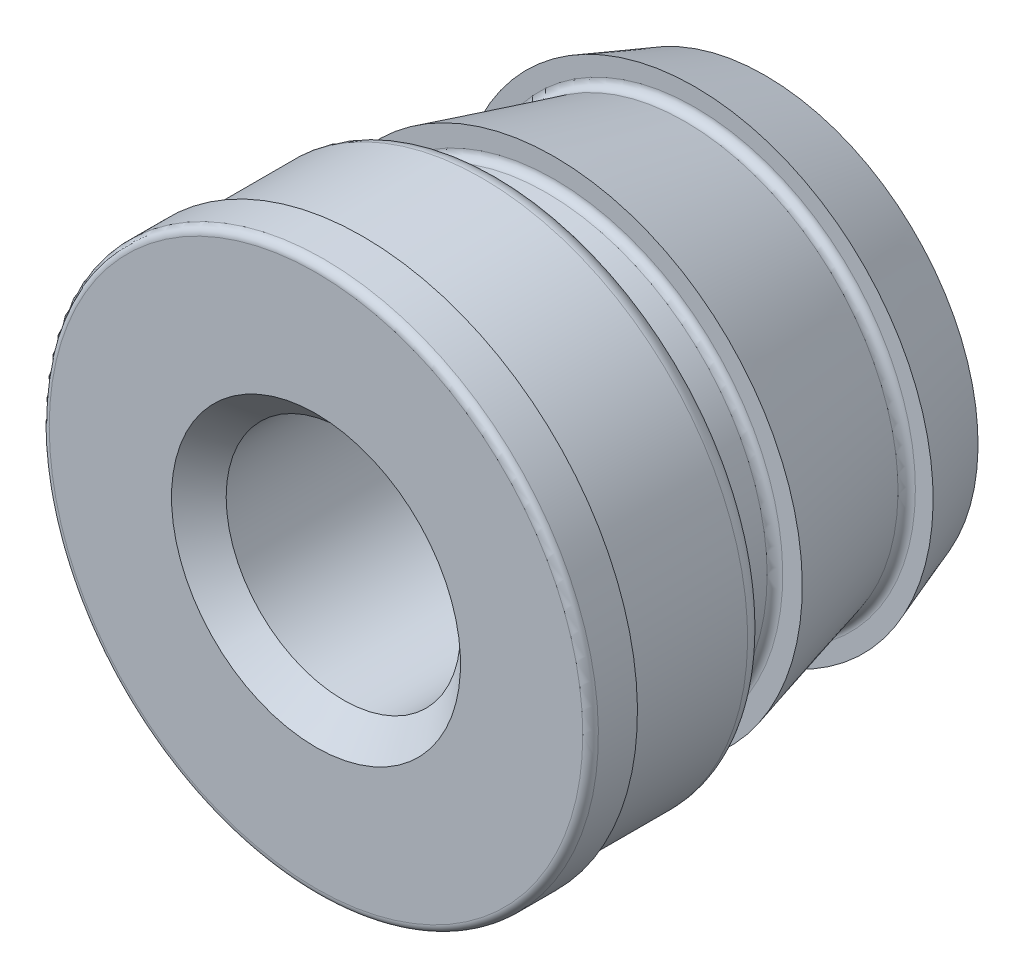
SolidWorks part; units mm, degrees
material "Brass"
ref_plane "Front Plane" through (0, 0, 0) normal (0, 0, 1) x (1, 0, 0)
ref_plane "Top Plane" through (0, 0, 0) normal (0, 1, 0) x (1, 0, 0)
ref_plane "Right Plane" through (0, 0, 0) normal (1, 0, 0) x (0, 0, -1)
sketch "Sketch1" plane through (0, 0, 0) normal (1, 0, 0) x (0, 0, -1)
  line L0 (1.4605, 0) -> (-1.4605, 0) construction
  line L1 (-1.4605, 1.7856) -> (-1.4605, -1.7856) construction
  line L2 (1.0033, -1.5494) -> (1.0033, 1.5494) construction
  line L3 (1.4605, 1.3843) -> (1.4605, -1.3843) construction
  line L4 (-1.4605, 1.7856) -> (-1.1557, 1.7856) construction
  line L5 (-1.1557, 1.7856) -> (-1.1557, 1.7272) construction
  line L6 (-1.1557, 1.7272) -> (-0.2667, 1.7272) construction
  line L7 (-0.2667, 1.7272) -> (-0.2667, 1.4351) construction
  line L8 (-0.2667, 1.4351) -> (0.0889, 1.4351) construction
  line L9 (0.0889, 1.4351) -> (0.0889, 1.6129) construction
  line L10 (0.0889, 1.6129) -> (1.0033, 1.3679) construction
  line L12 (-1.4605, -0.9398) -> (-1.2827, -0.762) construction
  line L13 (-1.2827, -0.762) -> (1.2827, -0.762) construction
  line L14 (1.2827, -0.762) -> (1.4605, -0.9398) construction
  line L15 (-1.2827, -0.762) -> (-1.2827, -0.4445) construction
  point P4 (0, 0)
  point P11 (1.0033, 0)
  dimension "Diameter (A)" = 3.5712
  dimension "Diameter (B)" = 3.0988
  dimension "End OD" = 2.7686
  dimension "Installed Length" = 2.921
  dimension "Head Length" = 0.3048
  dimension "Knurl Band OD" = 3.4544
  dimension "Knurl Band Length" = 0.889
  dimension "Relief Depth" = 0.2921
  dimension "Relief Length" = 0.3556
  dimension "Barb Length" = 0.9144
  dimension "Barb OD" = 3.2258
  dimension "Barb Angle" = 15
  dimension "Thread Size" = 1.524
  dimension "Thread Pitch" = 0.3175
  dimension "C'Sink" = 45
  dimension "C'Sink Dia" = 1.8796
sketch "Sketch2" plane through (0, 0, 0) normal (1, 0, 0) x (0, 0, -1)
  line L0 (1.4605, 0) -> (-1.4605, 0) construction
  line L1 (1.4605, 0) -> (-1.4605, 0) construction
  line L2 (-1.4605, 0.9398) -> (-1.4605, 1.7348)
  line L3 (-1.4605, 1.7856) -> (-1.4605, -1.7856) construction
  line L4 (-1.4097, 1.7856) -> (-1.1557, 1.7856)
  line L5 (-1.1557, 1.7856) -> (-1.1557, 1.7272)
  line L6 (-1.1557, 1.7272) -> (-0.381, 1.7272)
  line L7 (-0.2667, 1.6129) -> (-0.2667, 1.4859)
  line L8 (-0.2159, 1.4351) -> (0.0381, 1.4351)
  line L9 (0.0889, 1.4859) -> (0.0889, 1.6129)
  line L10 (0.0889, 1.6129) -> (0.9394, 1.385)
  line L11 (1.0033, 1.4341) -> (1.0033, 1.5494)
  line L15 (0.0889, 1.6129) -> (-0.2667, 1.6129) construction
  line L17 (1.0033, 1.5494) -> (1.4605, 1.3843)
  line L18 (1.4605, 1.3843) -> (1.4605, 0.9398)
  line L19 (1.4605, 1.3843) -> (1.4605, -1.3843) construction
  line L20 (1.4605, 0.9398) -> (1.2827, 0.762)
  line L21 (1.2827, 0.762) -> (-1.2827, 0.762)
  line L31 (1.2827, -0.762) -> (1.2827, 0.762) construction
  line L32 (-1.4605, 0.9398) -> (-1.2827, 0.762)
  line L33 (-1.4605, -0.9398) -> (-1.2827, -0.762) construction
  line L34 (1.2827, -0.762) -> (1.4605, -0.9398) construction
  arc A0 (-0.381, 1.7272) -> (-0.2667, 1.6129) centre (-0.381, 1.6129) cw
  arc A1 (-1.4605, 1.7348) -> (-1.4097, 1.7856) centre (-1.4097, 1.7348) cw
  arc A2 (0.9394, 1.385) -> (1.0033, 1.4341) centre (0.9525, 1.4341) ccw
  arc A3 (0.0381, 1.4351) -> (0.0889, 1.4859) centre (0.0381, 1.4859) ccw
  arc A4 (-0.2667, 1.4859) -> (-0.2159, 1.4351) centre (-0.2159, 1.4859) ccw
  point P23 (-0.2667, 1.7272)
  point P26 (-1.4605, 1.7856)
  point P37 (1.0033, 1.3679)
  point P42 (0.0889, 1.4351)
  point P45 (1.2827, 0)
  point P52 (-0.2667, 1.4351)
  dimension "D1" = 0.0508
  dimension "D2" = 0.0508
revolve "Revolve1" add sketch "Sketch2" angle 360 about L1
sketch "Sketch3" plane through (0, 0, 1.4605) normal (0, 0, 1) x (1, 0, 0)
  line L0 (0, -0.762) -> (0, 0) construction
  line L1 (0, 0) -> (0.381, -0.6599) construction
  circle A0 centre (0, 0) radius 0.762 construction
  point P0 (0.381, -0.6599)
  dimension "D1" = 30
sketch "Sketch4" [suppressed] plane through (0, 0, 1.4605) normal (0, 0, 1) x (1, 0, 0)
  circle A0 centre (0, 0) radius 0.762 construction
  circle A1 centre (0, 0) radius 0.762
curve "Helix/Spiral1" [suppressed] pitch 0.3175 height 3.2385 turns 10.2
sketch "Sketch5" [suppressed] plane through (0, 0, 0) normal (1, 0, 0) x (0, 0, -1)
  line L0 (-1.7582, 0.7792) -> (-1.5994, 0.5042) construction
  line L1 (-1.5994, 0.5042) -> (-1.4407, 0.7792) construction
  line L2 (-1.4407, 0.7792) -> (-1.7582, 0.7792) construction
  line L3 (-1.7383, 0.7448) -> (-1.4605, 0.7448) construction
  line L4 (-1.5994, 0.7792) -> (-1.5994, 0.7448) construction
  line L5 (-1.5994, 0.7448) -> (-1.5994, 0.5386) construction
  line L6 (-1.5994, 0.5386) -> (-1.5994, 0.5042) construction
  line L7 (-1.6192, 0.5386) -> (-1.5796, 0.5386)
  line L8 (-1.7482, 0.762) -> (-1.4506, 0.762)
  line L9 (-1.5796, 0.5386) -> (-1.4506, 0.762)
  line L10 (-1.6192, 0.5386) -> (-1.7482, 0.762)
  line L11 (-1.4605, 1.7856) -> (-1.4605, -1.7856) construction
  line L12 (1.2827, 0.762) -> (-1.2827, 0.762) construction
  point P12 (-1.5994, 0.762)
  dimension "D1" = 0.3175
  dimension "D2" = 0.0397
sweep "Sweep1" [suppressed] add profiles "Sketch5" path "Helix/Spiral1"
sketch "Sketch6" [suppressed] plane through (0, 0, 1.4605) normal (0, 0, 1) x (1, 0, 0)
  circle A0 centre (0, 0) radius 0.9398
extrude "Cut-Extrude1" [suppressed] cut sketch "Sketch6" against normal through all draft 45 and the other way through all
sketch "Sketch7" [suppressed] plane through (0, 0, -1.4605) normal (0, 0, -1) x (-1, 0, 0)
  circle A0 centre (0, 0) radius 0.9398 construction
  circle A1 centre (0, 0) radius 0.9398
extrude "Cut-Extrude2" [suppressed] cut sketch "Sketch7" against normal through all draft 45 and the other way through all
ref_plane "Plane2" [suppressed] through (0, 0, 1.1557) normal (0, 0, 1) x (1, 0, 0)
sketch "Sketch8" [suppressed] plane through (0, 0, 1.1557) normal (0, 0, 1) x (1, 0, 0)
  line L1 (-0.0359, 1.7123) -> (-0.1416, 1.6067)
  line L4 (0.1416, 1.6067) -> (0.0359, 1.7123)
  line L5 (-0.0533, 1.4242) -> (0.0029, 1.4805) [skipped]
  line L6 (-0.2728, 1.7504) -> (-0.2691, 1.7467) [skipped]
  circle A0 centre (0, 1.6129) radius 0.0957 construction
  circle A2 centre (0, 0) radius 1.6129 construction
  circle A3 centre (0, 0) radius 1.6129 construction
  arc A5 (0.1416, 1.6067) -> (-0.1416, 1.6067) centre (0, 0) ccw
  arc A6 (-0.0359, 1.7123) -> (0.0359, 1.7123) centre (0, 1.6764) cw
  circle A7 centre (0, 0) radius 1.7272 construction
  dimension "D1" = 0.0508
sketch "Sketch9" [suppressed] plane through (0, 0, 1.1557) normal (0, 0, 1) x (1, 0, 0)
  circle A0 centre (0, 0) radius 1.7272 construction
  circle A1 centre (0, 0) radius 1.7272
curve "Helix/Spiral2" [suppressed] pitch 19.3964 height 1.0668 turns 0.055
sketch "Sketch10" [suppressed] plane through (0, 0, 1.1557) normal (0, 0, -1) x (-1, 0, 0)
  circle A0 centre (0, 0) radius 1.6129 construction
  circle A1 centre (0, 0) radius 1.6129
  circle A2 centre (0, 0) radius 1.7272 construction
  circle A3 centre (0, 0) radius 1.7272
extrude "Cut-Extrude3" [suppressed] cut sketch "Sketch10" along normal up to surface (0.889 mm away)
sweep "Sweep2" [suppressed] add profiles "Sketch8" path "Helix/Spiral2"
pattern_circular "CirPattern1" [suppressed] count 16 over 360 of bodies 115
mirror "Mirror1" [suppressed] about plane through (0, 0, 0) normal (1, 0, 0)
sketch "Sketch11" [suppressed] plane through (0, 0, 0) normal (1, 0, 0) x (0, 0, -1)
  line L1 (-0.2667, 1.6129) -> (-0.2667, 1.4859)
  line L4 (-0.381, 1.7272) -> (-0.381, 1.7856)
  line L5 (-0.381, 1.7856) -> (0.0889, 1.7856)
  line L6 (0.0889, 1.7856) -> (0.0889, 1.4859)
  line L7 (-1.4097, 1.7856) -> (-1.1557, 1.7856) construction
  line L8 (1.4605, 0) -> (-1.4605, 0) construction
  line L9 (1.4605, 0) -> (-1.4605, 0) construction
  line L10 (-0.2159, 1.4351) -> (0.0381, 1.4351) construction
  line L11 (-0.2159, 1.4351) -> (0.0381, 1.4351)
  arc A0 (-0.2667, 1.6129) -> (-0.381, 1.7272) centre (-0.381, 1.6129) ccw construction
  arc A1 (-0.2667, 1.6129) -> (-0.381, 1.7272) centre (-0.381, 1.6129) ccw
  arc A2 (-0.2667, 1.4859) -> (-0.2159, 1.4351) centre (-0.2159, 1.4859) ccw construction
  arc A3 (0.0381, 1.4351) -> (0.0889, 1.4859) centre (0.0381, 1.4859) ccw construction
  arc A4 (-0.2667, 1.4859) -> (-0.2159, 1.4351) centre (-0.2159, 1.4859) ccw
  arc A5 (0.0381, 1.4351) -> (0.0889, 1.4859) centre (0.0381, 1.4859) ccw
revolve "Cut-Revolve1" [suppressed] cut sketch "Sketch11" angle 360 about L9
equation "\"D3@Helix/Spiral1\"=\"Installed Length@Sketch1\" + \"Thread Pitch@Sketch1\""
equation "\"D4@Helix/Spiral1\"=\"Thread Pitch@Sketch1\""
equation "\"D2@Sketch5\" = \"D1@Sketch5\" / 8"
equation "\"D1@Sketch5\" = \"Thread Pitch@Sketch1\""
equation "\"D3@Helix/Spiral2\"=\"Knurl Band Length@Sketch1\" + (\"Relief Length@Sketch1\" / 2)"
equation "\"D3@Cut-Extrude1\"=\"C'Sink@Sketch1\""
equation "\"D3@Cut-Extrude2\"=\"C'Sink@Sketch1\""
